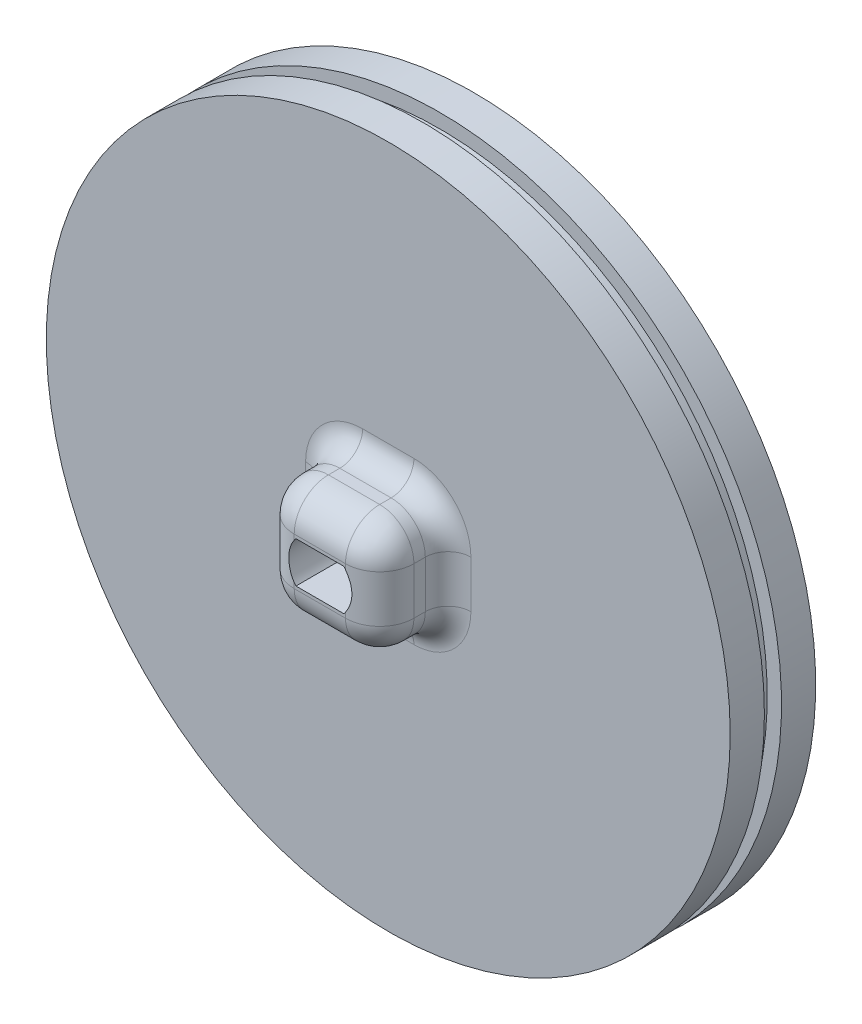
SolidWorks part; units mm, degrees
ref_plane "Plan de face" through (0, 0, 0) normal (0, 0, 1) x (1, 0, 0)
ref_plane "Plan de dessus" through (0, 0, 0) normal (0, 1, 0) x (1, 0, 0)
ref_plane "Plan de droite" through (0, 0, 0) normal (1, 0, 0) x (0, 0, -1)
sketch "Esquisse2" plane through (0, 0, 0) normal (0, 0, 1) x (1, 0, 0)
  line L0 (0, 0) -> (39.5063, 0) construction
  circle A0 centre (0, 0) radius 30
  dimension "D1" = 60
extrude "Boss.-Extru.1" add sketch "Esquisse2" along normal blind 3
sketch "Esquisse4" plane through (0, 0, 3) normal (0, 0, 1) x (1, 0, 0)
  line L1 (-2.1, -1.8) -> (2.1, -1.8)
  line L2 (-2.1, -1.8) -> (-2.1, 1.8) construction
  line L3 (-2.1, 1.8) -> (2.1, 1.8)
  line L4 (2.1, -1.8) -> (2.1, 1.8) construction
  line L5 (-2.1, -1.8) -> (2.1, 1.8) construction
  line L6 (-2.1, 1.8) -> (2.1, -1.8) construction
  arc A0 (-2.1, -1.8) -> (-2.1, 1.8) centre (0, 0) cw
  arc A1 (2.1, 1.8) -> (2.1, -1.8) centre (0, 0) cw
  point P0 (0, 0)
  dimension "D1" = 4.2
  dimension "D2" = 3.6
extrude "Enlèv. mat.-Extru.1" cut sketch "Esquisse4" against normal through all
sketch "Esquisse5" plane through (0, 0, 3) normal (0, 0, 1) x (1, 0, 0)
  line L0 (-2.1, 1.8) -> (2.1, 1.8)
  line L1 (5.2507, -5.0723) -> (-5.2507, -5.0723)
  line L2 (5.2507, -5.0723) -> (5.2507, 5.0723)
  line L3 (5.2507, 5.0723) -> (-5.2507, 5.0723)
  line L4 (-5.2507, -5.0723) -> (-5.2507, 5.0723)
  line L5 (5.2507, -5.0723) -> (-5.2507, 5.0723) construction
  line L6 (5.2507, 5.0723) -> (-5.2507, -5.0723) construction
  line L7 (-2.1, -1.8) -> (2.1, -1.8) construction
  line L8 (-2.1, -1.8) -> (2.1, -1.8)
  arc A0 (-2.1, -1.8) -> (-2.1, 1.8) centre (0, 0) cw
  arc A1 (2.1, 1.8) -> (2.1, -1.8) centre (0, 0) cw
  point P0 (0, 0)
  arc M1 (2.1, 1.8) -> (2.1, -1.8) centre (0, 0) cw
  line M2 (2.1, -1.8) -> (-2.1, -1.8)
  arc M3 (-2.1, -1.8) -> (-2.1, 1.8) centre (0, 0) cw
  line M4 (-2.1, 1.8) -> (2.1, 1.8)
extrude "Boss.-Extru.3" add sketch "Esquisse5" along normal blind 6 contours L4 L1 L2 L3 M4 M1 M2 M3 region at (0, -4.9263, 3)
sketch "Esquisse8" plane through (0, 0, 0) normal (0, 0, -1) x (-1, 0, 0)
  circle A0 centre (0, 0) radius 28.75
  dimension "D1" = 57.5
extrude "Boss.-Extru.4" add sketch "Esquisse8" along normal blind 1.5
sketch "Esquisse9" plane through (0, 0, -1.5) normal (0, 0, -1) x (-1, 0, 0)
  circle A0 centre (0, 0) radius 30
  dimension "D1" = 60
extrude "Boss.-Extru.5" add sketch "Esquisse9" along normal blind 3
sketch "Esquisse10" plane through (0, 0, 0) normal (0, 0, 1) x (1, 0, 0)
  line L0 (-2.1, 1.8) -> (2.1, 1.8)
  line L2 (2.1, -1.8) -> (-2.1, -1.8)
  line L3 (2.1, -1.8) -> (-2.1, -1.8) construction
  line L4 (-2.1, -1.8) -> (2.1, -1.8) construction
  arc A0 (-2.1, 1.8) -> (-2.1, -1.8) centre (0, 0) ccw
  arc A1 (-2.1, 1.8) -> (-2.1, -1.8) centre (0, 0) ccw construction
  arc A2 (2.1, 1.8) -> (2.1, -1.8) centre (0, 0) cw
  arc A3 (2.1, -1.8) -> (2.1, 1.8) centre (0, 0) ccw construction
  dimension "D2" = 2.7659
  dimension "D3" = 4.2
  dimension "D1" = 3.6
extrude "Enlèv. mat.-Extru.4" cut sketch "Esquisse10" against normal through all
fillet "Congé1" radius 3 8 edges at (-5.2507, 5.0723, 6) (-5.2507, -5.0723, 6) (-5.2507, 0, 9) (0, -5.0723, 9) (5.2507, -5.0723, 6) (5.2507, 0, 9) (5.2507, 5.0723, 6) (0, 5.0723, 9)
fillet "Congé2" radius 2 8 edges at (4.372, 4.1936, 3) (5.2507, 0, 3) (4.372, -4.1936, 3) (0, -5.0723, 3) (-4.372, -4.1936, 3) (-5.2507, 0, 3) (-4.372, 4.1936, 3) (0, 5.0723, 3)
